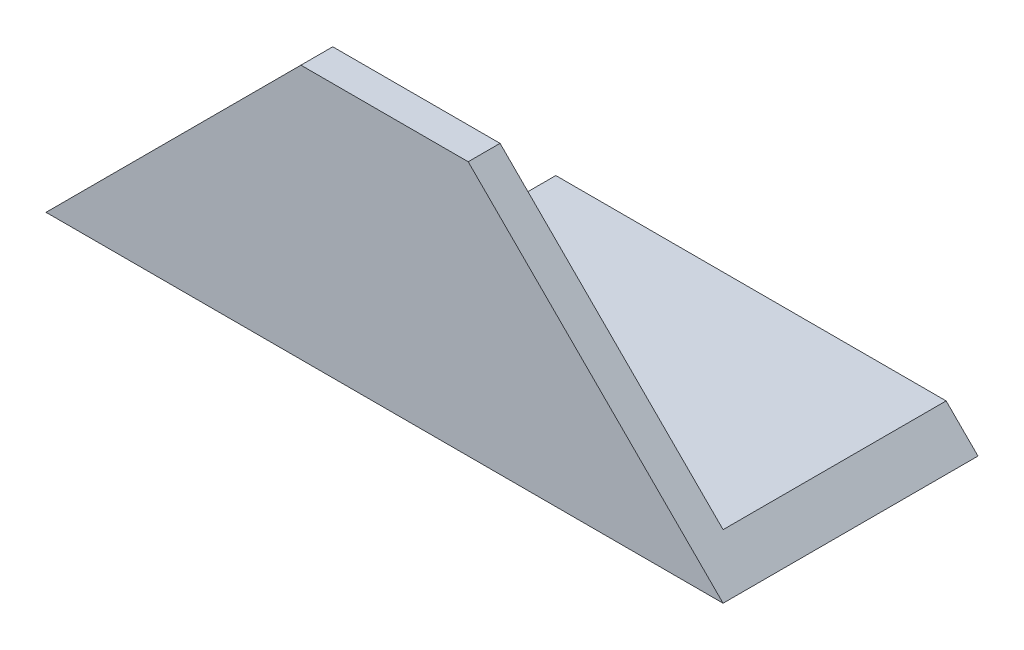
SolidWorks part; units mm, degrees
ref_plane "Спереди" through (0, 0, 0) normal (0, 0, 1) x (1, 0, 0)
ref_plane "Сверху" through (0, 0, 0) normal (0, 1, 0) x (1, 0, 0)
ref_plane "Справа" through (0, 0, 0) normal (1, 0, 0) x (0, 0, -1)
sketch "Эскиз1" plane through (0, 0, 0) normal (1, 0, 0) x (0, 0, -1)
  line L0 (0, 0) -> (32, 0)
  line L1 (0, 0) -> (0, 32)
extrude "Вытянуть-Тонкостенный1" add sketch "Эскиз1" along normal blind 85 thin thin type one direction wall 4
sketch "Эскиз2" plane through (0, 0, 0) normal (0, 0, 1) x (1, 0, 0)
  line L0 (0, 0) -> (0, 32)
  line L1 (0, 32) -> (32, 32)
  line L2 (85, 32) -> (0, 32) construction
  line L3 (32, 32) -> (0, 0)
  line L4 (85, 0) -> (0, 0) construction
  line L5 (53, 32) -> (85, 32)
  line L6 (85, 32) -> (85, 0)
  line L7 (85, 0) -> (85, 32) construction
  line L9 (85, 0) -> (53, 32)
extrude "Вырез-Вытянуть1" cut sketch "Эскиз2" against normal through all
sketch "Эскиз3" plane through (0, 0, 0) normal (0, -1, 0) x (1, 0, 0)
  line L1 (0, -32) -> (32, -32)
  line L2 (0, -32) -> (0, -4)
  line L3 (0, -4) -> (32, -4)
  line L4 (32, -32) -> (32, -4)
extrude "Вырез-Вытянуть2" cut sketch "Эскиз3" against normal blind 10
